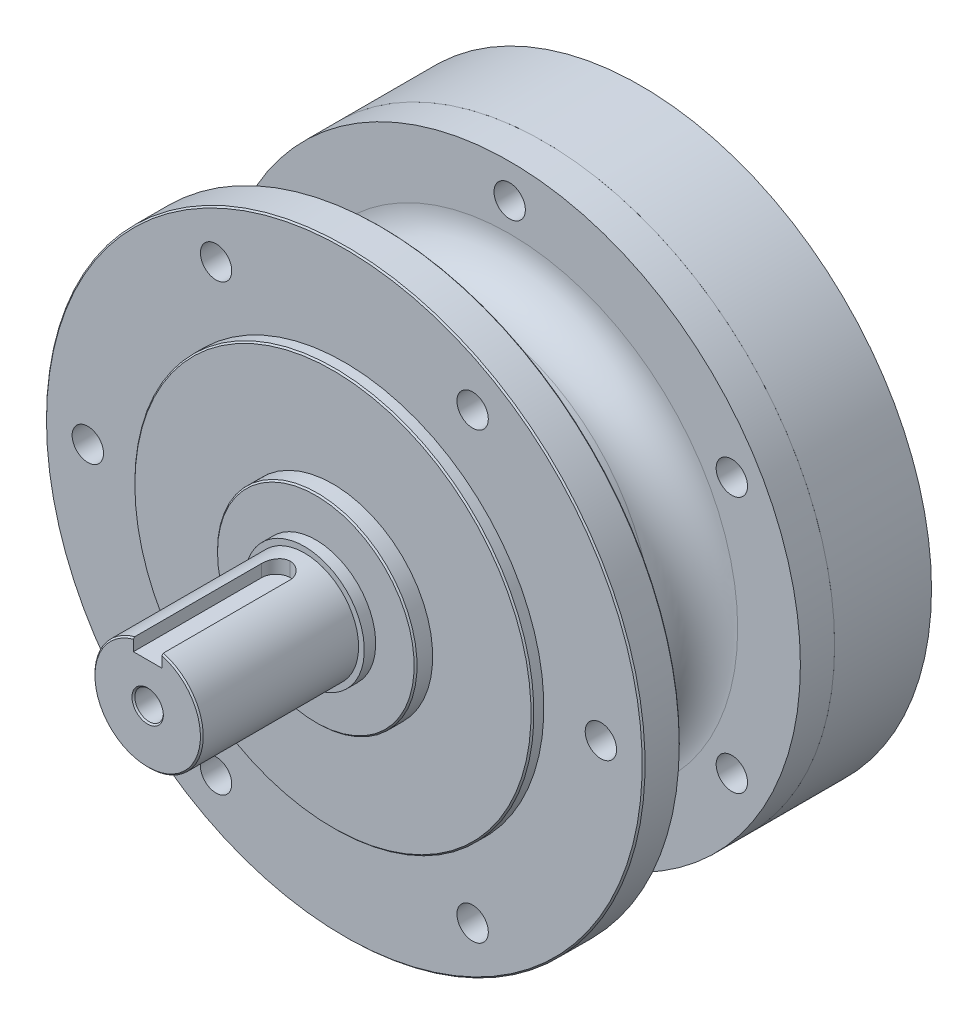
SolidWorks part; units mm, degrees
ref_plane "前视基准面" through (0, 0, 0) normal (0, 0, 1) x (1, 0, 0)
ref_plane "上视基准面" through (0, 0, 0) normal (0, 1, 0) x (1, 0, 0)
ref_plane "右视基准面" through (0, 0, 0) normal (1, 0, 0) x (0, 0, -1)
sketch "草图1" plane through (0, 0, 0) normal (0, 0, 1) x (1, 0, 0)
  circle A0 centre (0, 0) radius 105
  dimension "D1" = 210
extrude "拉伸1" add sketch "草图1" along normal blind 13
sketch "草图2" plane through (0, 0, 13) normal (0, 0, 1) x (1, 0, 0)
  circle A0 centre (0, 0) radius 70
extrude "拉伸2" add sketch "草图2" along normal blind 4
sketch "草图3" plane through (0, 0, 17) normal (0, 0, 1) x (1, 0, 0)
  circle A0 centre (0, 0) radius 35
  dimension "D1" = 70
extrude "拉伸3" add sketch "草图3" along normal blind 6
sketch "草图5" plane through (0, 0, 23) normal (0, 0, 1) x (1, 0, 0)
  circle A0 centre (0, 0) radius 21
  dimension "D1" = 42
extrude "拉伸4" add sketch "草图5" along normal blind 4
sketch "草图6" plane through (0, 0, 27) normal (0, 0, 1) x (1, 0, 0)
  circle A0 centre (0, 0) radius 19
extrude "拉伸5" add sketch "草图6" along normal blind 55
sketch "草图7" plane through (0, 0, 0) normal (0, 0, -1) x (-1, 0, 0)
  circle A0 centre (0, 0) radius 65
  dimension "D1" = 130
extrude "拉伸6" add sketch "草图7" along normal blind 45
sketch "草图8" plane through (0, 0, 0) normal (0, 0, -1) x (-1, 0, 0)
  circle A1 centre (90, 0) radius 5.5
  circle A3 centre (45, 77.9423) radius 5.5
  circle A4 centre (45, -77.9423) radius 5.5
  circle A5 centre (-45, -77.9423) radius 5.5
  circle A6 centre (-90, 0) radius 5.5
  circle A7 centre (-45, 77.9423) radius 5.5
extrude "切除-拉伸1" cut sketch "草图8" against normal blind 75
chamfer "倒角1" distance 0.5 angle 45 2 edges at (105, 0, 13) (105, 0, 0)
chamfer "倒角2" distance 0.5 angle 45 3 edges at (19, 0, 82) (35, 0, 23) (70, 0, 17)
sketch "草图9" plane through (0, 0, 82) normal (0, 0, 1) x (1, 0, 0)
  line L1 (-5, 19) -> (5, 19)
  line L2 (-5, 19) -> (-5, 14)
  line L3 (-5, 14) -> (5, 14)
  line L4 (5, 19) -> (5, 14)
  dimension "D2" = 10
  dimension "D3" = 5
extrude "切除-拉伸2" cut sketch "草图9" against normal blind 50
fillet "圆角1" radius 5 2 edges at (-5, 16.1652, 32) (5, 16.1652, 32)
sketch "草图10" plane through (0, 0, -45) normal (0, 0, -1) x (-1, 0, 0)
  circle A0 centre (0, 0) radius 102
extrude "拉伸7" add sketch "草图10" along normal blind 49
fillet "圆角2" radius 15 2 edges at (65, 0, 0) (-65, 0, -45)
sketch "草图11" plane through (0, 0, -94) normal (0, 0, -1) x (-1, 0, 0)
  circle A1 centre (0, 90) radius 5.5
  circle A2 centre (77.9423, 45) radius 5.5
  circle A3 centre (77.9423, -45) radius 5.5
  circle A4 centre (0, -90) radius 5.5
  circle A5 centre (-77.9423, -45) radius 5.5
  circle A6 centre (-77.9423, 45) radius 5.5
extrude "切除-拉伸3" cut sketch "草图11" against normal blind 55
sketch "草图12" plane through (0, 0, -94) normal (0, 0, -1) x (-1, 0, 0)
  circle A0 centre (0, 0) radius 69
  dimension "D1" = 138
extrude "切除-拉伸4" cut sketch "草图12" against normal blind 8
sketch "草图13" plane through (0, 0, -86) normal (0, 0, -1) x (-1, 0, 0)
  circle A0 centre (0, 0) radius 9
extrude "切除-拉伸5" cut sketch "草图13" against normal blind 50
sketch "草图14" plane through (0, 0, 0) normal (1, 0, 0) x (0, 0, -1)
  line L1 (94, 102) -> (45, 102) construction
  line L2 (57, 102) -> (57.01, 102)
  line L3 (57, 102) -> (57, -102)
  line L4 (57, -102) -> (57.01, -102)
  line L7 (57.01, 102) -> (57.01, -102)
  line L8 (45, -102) -> (94, -102) construction
  line L9 (45, 102) -> (45, -102) construction
  dimension "D1" = 0.01
  dimension "D2" = 12
extrude "切除-拉伸6" cut sketch "草图14" against normal blind 111 and the other way blind 161
sketch "草图15" plane through (0, 0, 82) normal (0, 0, 1) x (1, 0, 0)
  circle A0 centre (0, 0) radius 5
  dimension "D1" = 10
extrude "切除-拉伸7" cut sketch "草图15" against normal blind 30
chamfer "倒角3" distance 0.5 angle 45 1 edges at (5, 0, 82)
sketch "草图16" plane through (0, 0, -94) normal (0, 0, -1) x (-1, 0, 0)
  circle A0 centre (0, 0) radius 102
  circle A1 centre (0, 0) radius 82
  dimension "D1" = 164
extrude "切除-拉伸8" cut sketch "草图16" against normal blind 3
